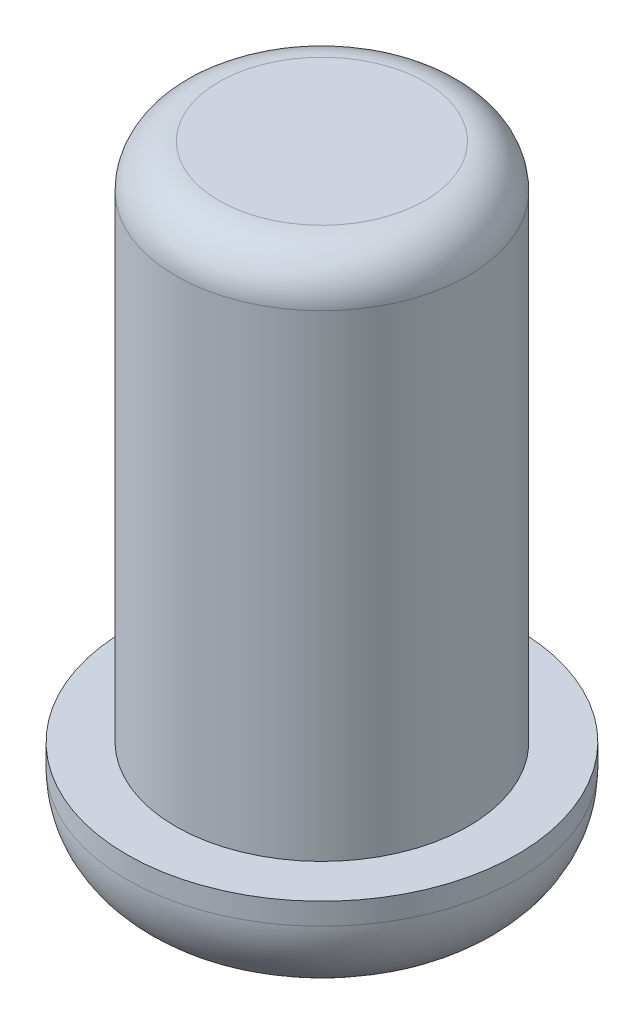
SolidWorks part; units mm, degrees
ref_plane "Front Plane" through (0, 0, 0) normal (0, 0, 1) x (1, 0, 0)
ref_plane "Top Plane" through (0, 0, 0) normal (0, 1, 0) x (1, 0, 0)
ref_plane "Right Plane" through (0, 0, 0) normal (1, 0, 0) x (0, 0, -1)
sketch "Sketch1" plane through (0, 0, 0) normal (0, 1, 0) x (1, 0, 0)
  circle A0 centre (0, 0) radius 0.675
  circle A1 centre (0, 0) radius 0.9
  dimension "D1" = 1.35
  dimension "D2" = 1.8
extrude "Boss-Extrude1" add sketch "Sketch1" along normal blind 2.4 contours A0
extrude "Boss-Extrude2" add sketch "Sketch1<3>" against normal blind 0.5 contours A1 A0 | A0 region at (0, 0, 0) region at (-0.8745, 0, 0)
sketch "Sketch1<3>" plane through (0, 0, 0) normal (0, 1, 0) x (1, 0, 0) same geometry as "Sketch1"
fillet "Fillet1" radius 0.4 1 edges at (0, -0.5, 0.9)
fillet "Fillet2" radius 0.2 1 edges at (0, 2.4, 0.675)
